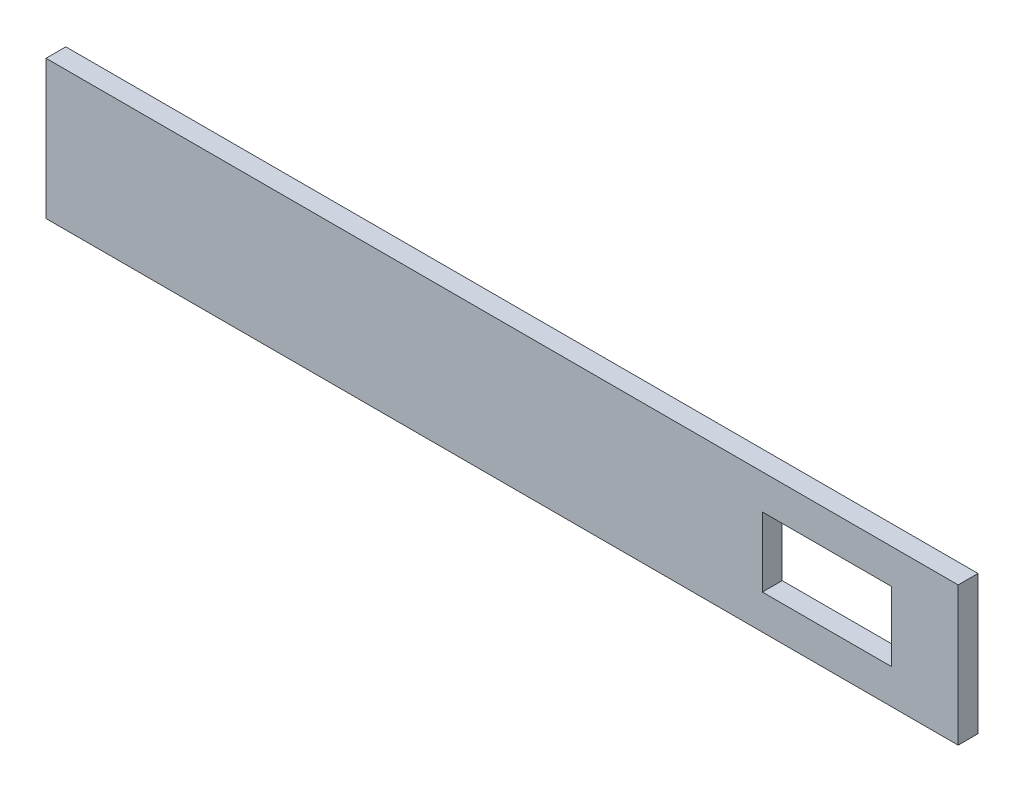
SolidWorks part; units mm, degrees
ref_plane "Front Plane" through (0, 0, 0) normal (0, 0, 1) x (1, 0, 0)
ref_plane "Top Plane" through (0, 0, 0) normal (0, 1, 0) x (1, 0, 0)
ref_plane "Right Plane" through (0, 0, 0) normal (1, 0, 0) x (0, 0, -1)
sketch "Sketch1" plane through (0, 0, 0) normal (0, 0, 1) x (1, 0, 0)
  line L0 (-250.033, -54.9538) -> (-250.033, 69.85) construction
  line L1 (42.067, 22.225) -> (-250.033, 22.225)
  line L2 (42.067, 22.225) -> (42.067, -22.225)
  line L3 (42.067, -22.225) -> (-250.033, -22.225)
  line L4 (-250.033, 22.225) -> (-250.033, -22.225)
  line L5 (63.0291, 0) -> (-62.7737, 0) construction
  line L6 (-19.6295, 10.033) -> (19.6295, 10.033) construction
  line L7 (19.6295, -10.033) -> (-19.6295, -10.033) construction
  dimension "D1" = 44.45
  dimension "D2" = 292.1
extrude "Boss-Extrude1" add sketch "Sketch1" along normal blind 6.35
sketch "Sketch2" plane through (0, 0, 6.35) normal (0, 0, 1) x (1, 0, 0)
  line L0 (-41.9443, 0) -> (30.2812, 0) construction
  line L1 (-20.6375, 11.1125) -> (20.6375, 11.1125)
  line L2 (-20.6375, 11.1125) -> (-20.6375, -11.1125)
  line L3 (-20.6375, -11.1125) -> (20.6375, -11.1125)
  line L4 (20.6375, 11.1125) -> (20.6375, -11.1125)
  line L5 (-19.6295, 10.033) -> (19.6295, 10.033) construction
  line L6 (19.6295, -10.033) -> (-19.6295, -10.033) construction
  line L7 (0, 34.6052) -> (0, -28.4279) construction
  line L8 (-20.1295, -9.533) -> (-20.1295, 9.533) construction
  line L9 (20.1295, 9.533) -> (20.1295, -9.533) construction
  dimension "D1" = 22.225
  dimension "D2" = 41.275
extrude "Cut-Extrude1" cut sketch "Sketch2" against normal through all
